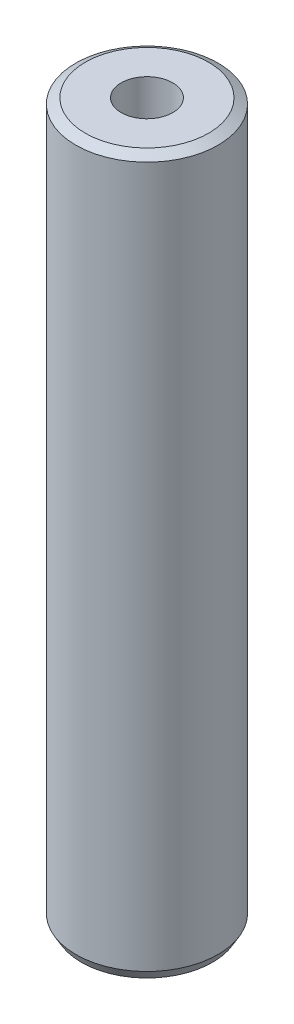
SolidWorks part; units mm, degrees
ref_plane "Front Plane" through (0, 0, 0) normal (0, 0, 1) x (1, 0, 0)
ref_plane "Top Plane" through (0, 0, 0) normal (0, 1, 0) x (1, 0, 0)
ref_plane "Right Plane" through (0, 0, 0) normal (1, 0, 0) x (0, 0, -1)
sketch "Sketch1" plane through (0, 0, 0) normal (0, 1, 0) x (1, 0, 0)
  circle A0 centre (0, 0) radius 57.5
  dimension "SHAFT_OD" = 115
extrude "Boss-Extrude1" add sketch "Sketch1" along normal blind 578.4966
sketch "Sketch2" plane through (0, 0, 0) normal (0, 1, 0) x (1, 0, 0)
  circle A0 centre (0, 0) radius 20.8581
  dimension "BORE_D" = 41.7161
extrude "Cut-Extrude1" cut sketch "Sketch2" along normal through all
chamfer "Chamfer1" distance 4.4654 angle 60 2 edges at (0, 578.4966, 57.5) (0, 0, 57.5) first distance on face at (0, 578.4966, 57.5) first distance on face at (0, 0, 20.8581)
